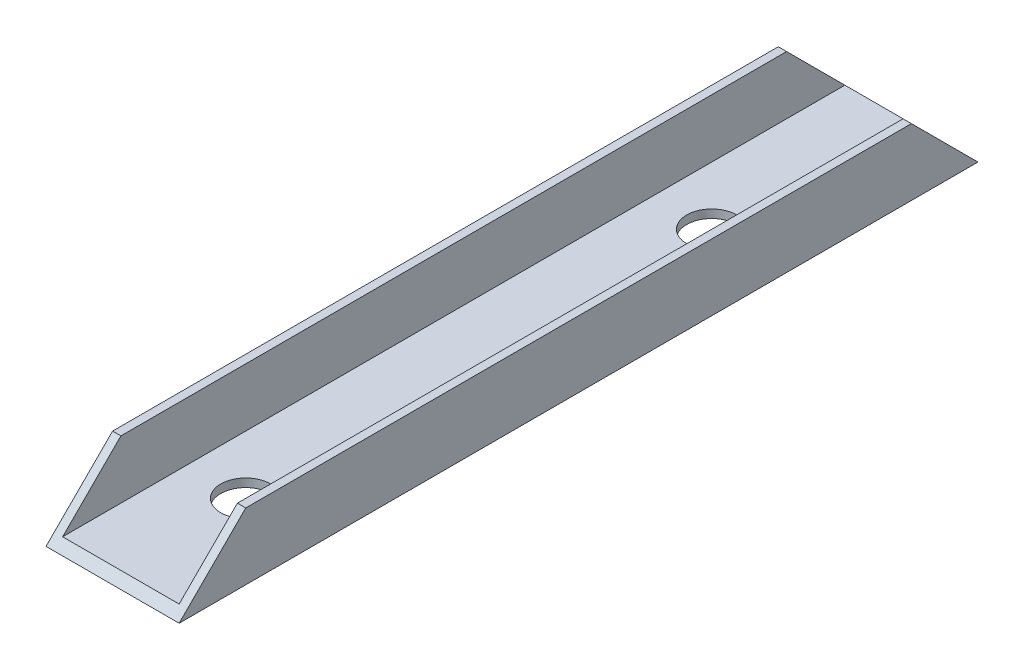
SolidWorks part; units mm, degrees
material "AISI 1010 Steel, hot rolled bar"
ref_plane "Front Plane" through (0, 0, 0) normal (0, 0, 1) x (1, 0, 0)
ref_plane "Top Plane" through (0, 0, 0) normal (0, 1, 0) x (1, 0, 0)
ref_plane "Right Plane" through (0, 0, 0) normal (1, 0, 0) x (0, 0, -1)
sketch "Sketch1" plane through (0, 0, 0) normal (0, 0, 1) x (1, 0, 0)
  line L0 (-25.4, 0) -> (25.4, 0)
  line L1 (25.4, 0) -> (25.4, 25.4)
  line L2 (25.4, 25.4) -> (22.225, 25.4)
  line L3 (22.225, 25.4) -> (22.225, 3.175)
  line L4 (22.225, 3.175) -> (-22.225, 3.175)
  line L5 (-22.225, 3.175) -> (-22.225, 25.4)
  line L6 (-22.225, 25.4) -> (-25.4, 25.4)
  line L7 (-25.4, 25.4) -> (-25.4, 0)
  line L8 (0, 15.5567) -> (0, -9.8218) construction
  dimension "D1" = 3.175
  dimension "D2" = 3.175
  dimension "D3" = 25.4
  dimension "D4" = 50.8
extrude "Boss-Extrude1" add sketch "Sketch1" along normal blind 304.8
sketch "Sketch2" plane through (25.4, 0, 0) normal (1, 0, 0) x (0, 0, -1)
  line L0 (-304.8, 0) -> (-279.4, 25.4)
  line L1 (-304.8, 25.4) -> (0, 25.4) construction
  line L2 (-279.4, 25.4) -> (-304.8, 25.4)
  line L3 (-304.8, 25.4) -> (-304.8, 0)
  line L4 (0, 0) -> (0, 25.4)
  line L5 (0, 25.4) -> (-25.4, 25.4)
  line L6 (-25.4, 25.4) -> (0, 0)
  dimension "D1" = 45
  dimension "D2" = 45
extrude "Cut-Extrude1" cut sketch "Sketch2" against normal through all
sketch "Sketch3" plane through (0, 0, 0) normal (0, -1, 0) x (1, 0, 0)
  line L0 (0, 304.8) -> (0, 0) construction
  line L1 (-25.4, 304.8) -> (25.4, 304.8) construction
  line L2 (-25.4, 0) -> (25.4, 0) construction
  circle A0 centre (0, 254) radius 9.525
  circle A1 centre (0, 76.2) radius 9.525
  dimension "D3" = 19.05
  dimension "D1" = 177.8
  dimension "D2" = 76.2
extrude "Cut-Extrude2" cut sketch "Sketch3" against normal blind 330.2
sketch "Sketch4" [suppressed] plane through (0, 0, 0) normal (0, -1, 0) x (1, 0, 0)
  line L0 (0, 381) -> (0, 0) construction
  line L1 (-25.4, 381) -> (25.4, 381) construction
  line L2 (-25.4, 190.5) -> (25.4, 190.5) construction
  line L3 (-13.97, 276.86) -> (13.97, 276.86)
  line L4 (-20.32, 276.86) -> (-20.32, 304.8)
  line L5 (-13.97, 304.8) -> (13.97, 304.8)
  line L6 (20.32, 276.86) -> (20.32, 304.8)
  line L7 (-20.32, 276.86) -> (20.32, 304.8) construction
  line L8 (-20.32, 304.8) -> (20.32, 276.86) construction
  line L9 (-25.4, 381) -> (-25.4, 0) construction
  line L10 (25.4, 381) -> (25.4, 0) construction
  line L11 (-20.32, 104.14) -> (-20.32, 76.2)
  line L12 (-13.97, 104.14) -> (13.97, 104.14)
  line L17 (-25.4, 290.83) -> (25.4, 290.83) construction
  line L18 (20.32, 104.14) -> (20.32, 76.2)
  line L19 (-13.97, 76.2) -> (13.97, 76.2)
  arc A0 (-13.97, 304.8) -> (-20.32, 304.8) centre (-17.145, 304.8) ccw
  arc A1 (13.97, 304.8) -> (20.32, 304.8) centre (17.145, 304.8) cw
  arc A2 (13.97, 276.86) -> (20.32, 276.86) centre (17.145, 276.86) ccw
  arc A3 (-13.97, 276.86) -> (-20.32, 276.86) centre (-17.145, 276.86) cw
  arc A4 (-13.97, 76.2) -> (-20.32, 76.2) centre (-17.145, 76.2) cw
  arc A5 (-13.97, 104.14) -> (-20.32, 104.14) centre (-17.145, 104.14) ccw
  arc A6 (13.97, 104.14) -> (20.32, 104.14) centre (17.145, 104.14) cw
  arc A7 (13.97, 76.2) -> (20.32, 76.2) centre (17.145, 76.2) ccw
  point P5 (0, 290.83)
  dimension "D4" = 6.35
  dimension "D1" = 27.94
  dimension "D2" = 40.64
  dimension "D3" = 76.2
extrude "Cut-Extrude3" [suppressed] cut sketch "Sketch4" against normal through all
equation "\"D2@Sketch1\"=\"D1@Sketch1\""
